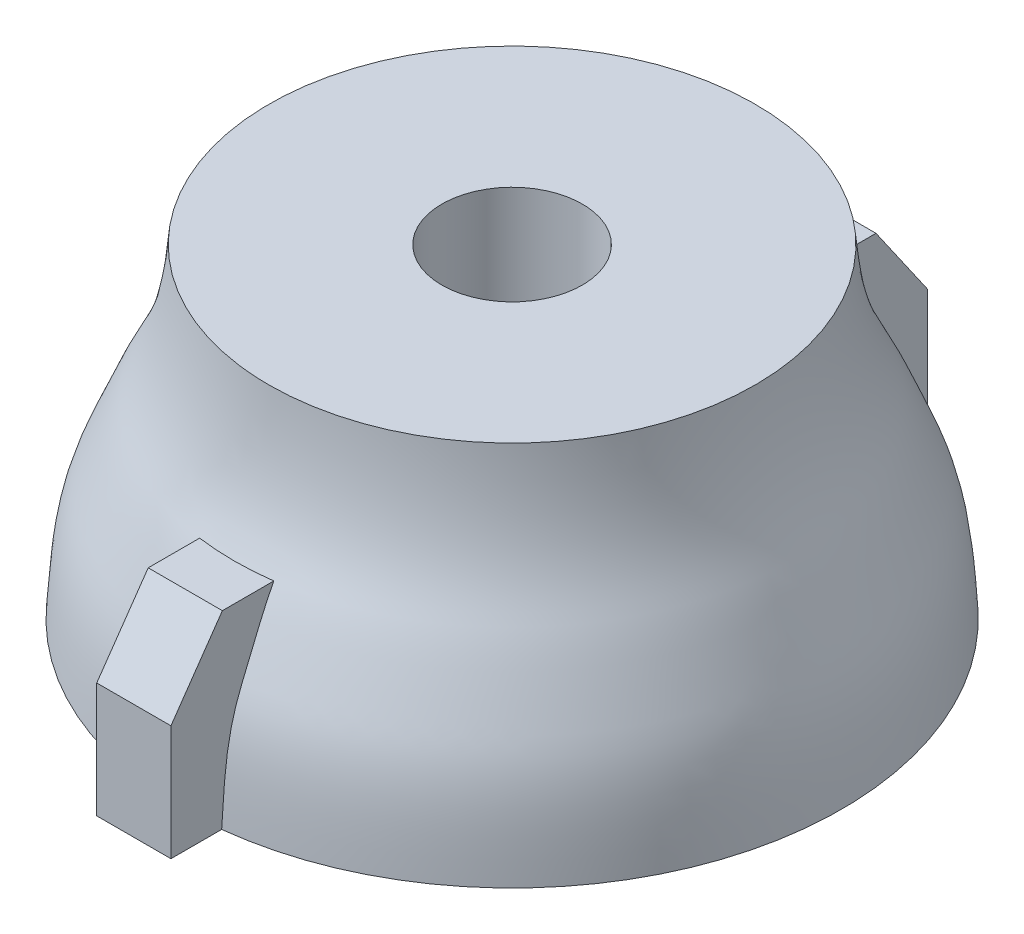
SolidWorks part; units mm, degrees
ref_plane "Front Plane" through (0, 0, 0) normal (0, 0, 1) x (1, 0, 0)
ref_plane "Top Plane" through (0, 0, 0) normal (0, 1, 0) x (1, 0, 0)
ref_plane "Right Plane" through (0, 0, 0) normal (1, 0, 0) x (0, 0, -1)
sketch "Sketch1" plane through (0, 0, 0) normal (0, 0, 1) x (1, 0, 0)
  line L0 (0, 43.5407) -> (0, -52.2489) construction
  line L1 (0, -18.2871) -> (-7.747, -18.2871)
  line L2 (0, -18.2871) -> (0, -10.6671)
  line L3 (0, -10.6671) -> (-5.715, -10.6671)
  spline S0 degree 3 poles (-5.715, -10.6671) (-5.8698, -12.708) (-6.3753, -13.4893) (-6.8126, -14.4258) (-7.1555, -15.2584) (-7.6136, -16.3971) (-7.6826, -17.1835) (-7.747, -18.2871) knots 0 0 0 0 0.274275 0.313988 0.387893 0.416791 0.593729 0.593729 0.593729 0.593729
  dimension "D1" = 7.747
  dimension "D2" = 7.62
  dimension "D3" = 5.715
revolve "Revolve1" add sketch "Sketch1" angle 360 about L0
sketch "Sketch2" plane through (0, 0, 0) normal (0, 0, 1) x (1, 0, 0)
  line L0 (-7.747, -18.2871) -> (7.747, -18.2871) construction
  line L1 (0.8718, -13.8421) -> (-0.8718, -13.8421)
  line L2 (0.8718, -13.8421) -> (0.8718, -18.2871)
  line L3 (0.8718, -18.2871) -> (-0.8718, -18.2871)
  line L4 (-0.8718, -13.8421) -> (-0.8718, -18.2871)
  line L5 (0.8718, -13.8421) -> (-0.8718, -18.2871) construction
  line L6 (0.8718, -18.2871) -> (-0.8718, -13.8421) construction
  point P0 (0, -16.0646)
  dimension "D1" = 4.445
extrude "Boss-Extrude1" add sketch "Sketch2" along normal blind 8.89 and the other way blind 8.89
sketch "Sketch3" plane through (0.8718, 0, 0) normal (1, 0, 0) x (0, 0, -1)
  line L0 (-7.681, -13.8421) -> (-8.89, -15.5811)
  line L1 (-6.472, -13.8421) -> (-8.89, -13.8421) construction
  line L2 (-8.89, -18.2871) -> (-8.89, -13.8421) construction
  line L3 (-8.89, -15.5811) -> (-8.89, -13.8421)
  line L4 (-8.89, -13.8421) -> (-7.681, -13.8421)
extrude "Cut-Extrude1" cut sketch "Sketch3" against normal through all
mirror "Mirror1" about plane through (0, 0, 0) normal (0, 0, 1) of "Cut-Extrude1"
sketch "Sketch4" plane through (0, -10.6671, 0) normal (0, 1, 0) x (1, 0, 0)
  circle A0 centre (0, 0) radius 1.651
  dimension "D1" = 3.302
extrude "Cut-Extrude2" cut sketch "Sketch4" against normal through all
